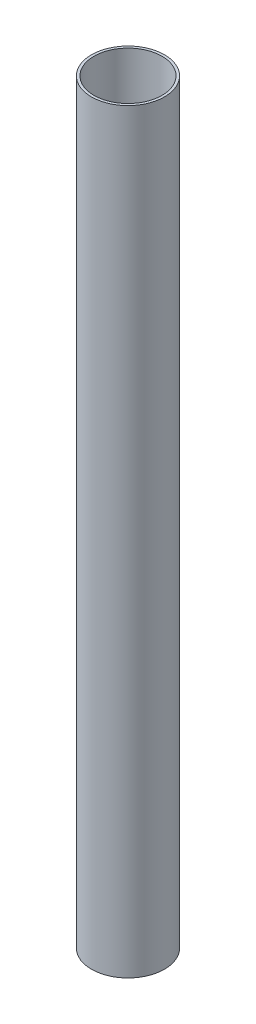
SolidWorks part; units mm, degrees
ref_plane "Front Plane" through (0, 0, 0) normal (0, 0, 1) x (1, 0, 0)
ref_plane "Top Plane" through (0, 0, 0) normal (0, 1, 0) x (1, 0, 0)
ref_plane "Right Plane" through (0, 0, 0) normal (1, 0, 0) x (0, 0, -1)
sketch "Sketch1" plane through (0, 0, 0) normal (0, 1, 0) x (1, 0, 0)
  circle A0 centre (0, 0) radius 27
  circle A1 centre (0, 0) radius 29
  dimension "D1" = 58
  dimension "D2" = 2
extrude "Boss-Extrude1" add sketch "Sketch1" along normal blind 600
